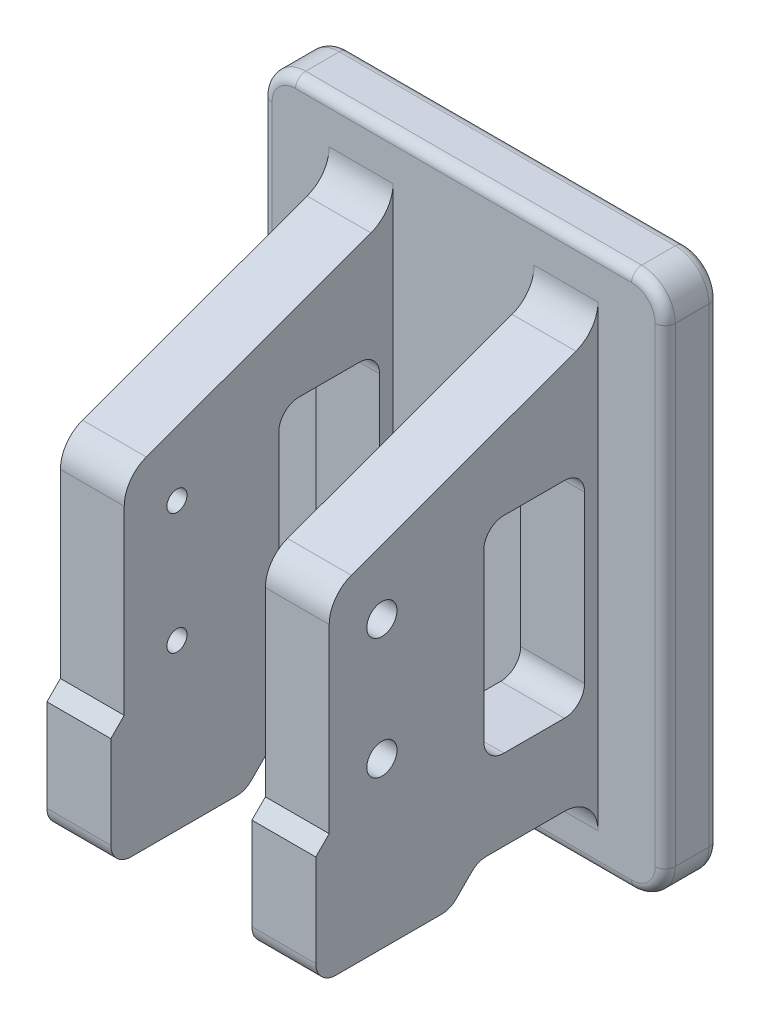
SolidWorks part; units mm, degrees
ref_plane "Front Plane" through (0, 0, 0) normal (0, 0, 1) x (1, 0, 0)
ref_plane "Top Plane" through (0, 0, 0) normal (0, 1, 0) x (1, 0, 0)
ref_plane "Right Plane" through (0, 0, 0) normal (1, 0, 0) x (0, 0, -1)
sketch "Sketch3" plane through (0, 0, 30) normal (0, 0, -1) x (-1, 0, 0)
  line L0 (95, 33.2573) -> (65, 33.2573) construction
  line L15 (80, 53.2573) -> (80, 33.2573) construction
  line L20 (55, 53.2573) -> (105, 53.2573)
  line L29 (55, -26.7427) -> (105, -26.7427)
  line L31 (110, -21.7427) -> (110, 48.2573)
  line L33 (50, -21.7427) -> (50, 48.2573)
  arc A17 (50, 48.2573) -> (55, 53.2573) centre (55, 48.2573) cw
  arc A18 (110, 48.2573) -> (105, 53.2573) centre (105, 48.2573) ccw
  arc A21 (50, -21.7427) -> (55, -26.7427) centre (55, -21.7427) ccw
  arc A22 (110, -21.7427) -> (105, -26.7427) centre (105, -21.7427) cw
  dimension "D1" = 5
extrude "Boss-Extrude1" add sketch "Sketch3" along normal blind 8
sketch "Sketch8" plane through (0, 0, 22) normal (0, 0, -1) x (-1, 0, 0)
  line L0 (50, 13.2573) -> (110, 13.2573) construction
  line L1 (50, 48.2573) -> (50, -21.7427) construction
  line L2 (110, -21.7427) -> (110, 48.2573) construction
  line L3 (80, 13.2573) -> (80, -26.7427) construction
  line L4 (55, -26.7427) -> (105, -26.7427) construction
  line L5 (78.25, 15.3786) -> (78.25, 11.136)
  line L6 (81.75, 15.3786) -> (81.75, 11.136)
  arc A0 (78.25, 11.136) -> (81.75, 11.136) centre (80, 13.2573) ccw
  arc A1 (81.75, 15.3786) -> (78.25, 15.3786) centre (80, 13.2573) ccw
extrude "Cut-Extrude3" cut sketch "Sketch8" against normal blind 3
sketch "Sketch10" plane through (0, 0, 22) normal (0, 0, -1) x (-1, 0, 0)
  line L0 (50, 13.2573) -> (110, 13.2573) construction
  line L1 (50, 48.2573) -> (50, -21.7427) construction
  line L2 (110, -21.7427) -> (110, 48.2573) construction
  line L3 (80, 13.2573) -> (80, -26.7427) construction
  line L4 (55, -26.7427) -> (105, -26.7427) construction
  line L7 (81.75, 11.136) -> (81.75, 15.3786)
  line L8 (78.25, 15.3786) -> (78.25, 11.136)
  line L9 (81.75, 11.136) -> (81.75, 15.3786)
  line L10 (78.25, 15.3786) -> (78.25, 11.136)
  circle A3 centre (80, 13.2573) radius 9.75
  arc A5 (78.25, 11.136) -> (81.75, 11.136) centre (80, 13.2573) ccw
  arc A6 (81.75, 15.3786) -> (78.25, 15.3786) centre (80, 13.2573) ccw
  arc A7 (78.25, 11.136) -> (81.75, 11.136) centre (80, 13.2573) ccw
  arc A8 (81.75, 15.3786) -> (78.25, 15.3786) centre (80, 13.2573) ccw
  dimension "D1" = 0
extrude "Boss-Extrude4" add sketch "Sketch10" along normal blind 9
fillet "Fillet2" radius 1.5 16 edges at (-80, -26.7427, 30) (-80, 53.2573, 30) (-50, 13.2573, 30) (-51.4645, 51.7928, 30) (-108.5355, 51.7928, 30) (-110, 13.2573, 30) (-80, -26.7427, 22) (-50, 13.2573, 22) (-51.4645, 51.7928, 22) (-80, 53.2573, 22) (-108.5355, 51.7928, 22) (-110, 13.2573, 22) (-108.5355, -25.2783, 22) (-51.4645, -25.2783, 22) (-108.5355, -25.2783, 30) (-51.4645, -25.2783, 30)
sketch "Sketch11" plane through (0, 0, 22) normal (0, 0, -1) x (-1, 0, 0)
  line L0 (50, 13.2573) -> (110, 13.2573) construction
  line L1 (50, -21.7427) -> (50, 48.2573) construction
  line L2 (110, 48.2573) -> (110, -21.7427) construction
  line L3 (80, 13.2573) -> (80, -26.7427) construction
  line L4 (105, -26.7427) -> (55, -26.7427) construction
  circle A0 centre (80, 13.2573) radius 11.75
extrude "Boss-Extrude5" add sketch "Sketch11" along normal blind 1
sketch "Sketch14" plane through (-70, 0, 0) normal (1, 0, 0) x (0, 0, -1)
  line L0 (-22, 1.5073) -> (-22, 25.0073) construction
  line L1 (-30, 48.2573) -> (-30, -21.7427) construction
  line L2 (-70, -1.7605) -> (-70, 28.6985)
  line L3 (-70, 28.6985) -> (-30, 43.2573)
  line L4 (-30, -16.3789) -> (-47.8764, -16.3789)
  line L6 (-30, -16.3789) -> (-30, 43.2573)
  line L7 (-47.8764, -16.3789) -> (-52, -20.5025)
  line L8 (-52, -20.5025) -> (-72, -20.5025)
  line L9 (-72, -20.5025) -> (-72, -3.7605)
  line L11 (-72, -3.7605) -> (-70, -1.7605)
  circle A6 centre (-62.1572, 3.9815) radius 1.5 construction
  circle A7 centre (-62.1572, 21.9815) radius 1.5 construction
  circle A8 centre (-62.1572, 3.9815) radius 1.5
  circle A9 centre (-62.1572, 21.9815) radius 1.5
extrude "Boss-Extrude7" add sketch "Sketch14" along normal blind 10
sketch "Sketch15" plane through (-90, 0, 0) normal (-1, 0, 0) x (0, 0, 1)
  line L4 (47.8764, -16.3789) -> (52, -20.5025)
  line L5 (70, -1.7605) -> (70, 28.6985)
  line L6 (70, 28.6985) -> (30, 43.2573)
  line L7 (30, 43.2573) -> (30, -16.3789)
  line L9 (70, -1.7605) -> (70, 28.6985)
  line L10 (70, 28.6985) -> (30, 43.2573)
  line L15 (30, 43.2573) -> (30, -16.3789)
  line L20 (47.8764, -16.3789) -> (52, -20.5025)
  line L21 (52, -20.5025) -> (72, -20.5025)
  line L22 (52, -20.5025) -> (72, -20.5025)
  line L23 (72, -20.5025) -> (72, -3.7605)
  line L24 (72, -20.5025) -> (72, -3.7605)
  line L25 (72, -3.7605) -> (70, -1.7605)
  line L26 (72, -3.7605) -> (70, -1.7605)
  line L27 (30, -16.3789) -> (47.8764, -16.3789)
  line L28 (30, -16.3789) -> (47.8764, -16.3789)
  circle A2 centre (62.1572, 3.9815) radius 1.5 construction
  circle A3 centre (62.1572, 21.9815) radius 1.5 construction
  circle A4 centre (62.1572, 3.9815) radius 1.5
  circle A5 centre (62.1572, 21.9815) radius 1.5
  dimension "D1" = 0
extrude "Boss-Extrude8" add sketch "Sketch15" along normal blind 10
fillet "Fillet3" radius 5 6 edges at (-65, 43.2573, 30) (-95, 43.2573, 30) (-95, 28.6985, 70) (-65, 28.6985, 70) (-95, -16.3789, 30) (-65, -16.3789, 30)
fillet "Fillet4" radius 3 6 edges at (-95, -20.5025, 72) (-65, -20.5025, 72) (-65, -20.5025, 52) (-95, -20.5025, 52) (-95, -16.3789, 47.8764) (-65, -16.3789, 47.8764)
sketch "Sketch16" plane through (-90, 0, 0) normal (1, 0, 0) x (0, 0, -1)
  line L8 (-72, -3.7605) -> (-72, -17.5025)
  line L9 (-69, -20.5025) -> (-53.2426, -20.5025)
  line L10 (-51.1213, -19.6238) -> (-48.7551, -17.2576)
  line L11 (-46.6337, -16.3789) -> (-35, -16.3789)
  line L12 (-30, -21.3789) -> (-30, 46.7583)
  line L13 (-33.2899, 42.0599) -> (-66.7101, 29.8959)
  line L14 (-70, 25.1974) -> (-70, -1.7605)
  line L15 (-70, -1.7605) -> (-72, -3.7605)
  line L16 (-72, -3.7605) -> (-72, -17.5025)
  line L17 (-69, -20.5025) -> (-53.2426, -20.5025)
  line L18 (-51.1213, -19.6238) -> (-48.7551, -17.2576)
  line L19 (-46.6337, -16.3789) -> (-35, -16.3789)
  line L20 (-30, -21.3789) -> (-30, 46.7583)
  line L21 (-33.2899, 42.0599) -> (-66.7101, 29.8959)
  line L22 (-70, 25.1974) -> (-70, -1.7605)
  line L23 (-70, -1.7605) -> (-72, -3.7605)
  arc A6 (-72, -17.5025) -> (-69, -20.5025) centre (-69, -17.5025) ccw
  arc A7 (-53.2426, -20.5025) -> (-51.1213, -19.6238) centre (-53.2426, -17.5025) ccw
  arc A8 (-46.6337, -16.3789) -> (-48.7551, -17.2576) centre (-46.6337, -19.3789) ccw
  arc A9 (-30, -21.3789) -> (-35, -16.3789) centre (-35, -21.3789) ccw
  arc A10 (-33.2899, 42.0599) -> (-30, 46.7583) centre (-35, 46.7583) ccw
  arc A11 (-66.7101, 29.8959) -> (-70, 25.1974) centre (-65, 25.1974) ccw
  arc A12 (-72, -17.5025) -> (-69, -20.5025) centre (-69, -17.5025) ccw
  arc A13 (-53.2426, -20.5025) -> (-51.1213, -19.6238) centre (-53.2426, -17.5025) ccw
  arc A14 (-46.6337, -16.3789) -> (-48.7551, -17.2576) centre (-46.6337, -19.3789) ccw
  arc A15 (-30, -21.3789) -> (-35, -16.3789) centre (-35, -21.3789) ccw
  arc A16 (-33.2899, 42.0599) -> (-30, 46.7583) centre (-35, 46.7583) ccw
  arc A17 (-66.7101, 29.8959) -> (-70, 25.1974) centre (-65, 25.1974) ccw
  dimension "D1" = 0
extrude "Cut-Extrude4" cut sketch "Sketch16" against normal blind 0.25
sketch "Sketch17" plane through (-70, 0, 0) normal (-1, 0, 0) x (0, 0, 1)
  line L8 (53.2426, -20.5025) -> (69, -20.5025)
  line L9 (72, -17.5025) -> (72, -3.7605)
  line L10 (72, -3.7605) -> (70, -1.7605)
  line L11 (70, -1.7605) -> (70, 25.1974)
  line L12 (66.7101, 29.8959) -> (33.2899, 42.0599)
  line L13 (30, 46.7583) -> (30, -21.3789)
  line L14 (35, -16.3789) -> (46.6337, -16.3789)
  line L15 (48.7551, -17.2576) -> (51.1213, -19.6238)
  line L16 (53.2426, -20.5025) -> (69, -20.5025)
  line L17 (72, -17.5025) -> (72, -3.7605)
  line L18 (72, -3.7605) -> (70, -1.7605)
  line L19 (70, -1.7605) -> (70, 25.1974)
  line L20 (66.7101, 29.8959) -> (33.2899, 42.0599)
  line L21 (30, 46.7583) -> (30, -21.3789)
  line L22 (35, -16.3789) -> (46.6337, -16.3789)
  line L23 (48.7551, -17.2576) -> (51.1213, -19.6238)
  arc A6 (69, -20.5025) -> (72, -17.5025) centre (69, -17.5025) ccw
  arc A7 (70, 25.1974) -> (66.7101, 29.8959) centre (65, 25.1974) ccw
  arc A8 (30, 46.7583) -> (33.2899, 42.0599) centre (35, 46.7583) ccw
  arc A9 (35, -16.3789) -> (30, -21.3789) centre (35, -21.3789) ccw
  arc A10 (48.7551, -17.2576) -> (46.6337, -16.3789) centre (46.6337, -19.3789) ccw
  arc A11 (51.1213, -19.6238) -> (53.2426, -20.5025) centre (53.2426, -17.5025) ccw
  arc A12 (69, -20.5025) -> (72, -17.5025) centre (69, -17.5025) ccw
  arc A13 (70, 25.1974) -> (66.7101, 29.8959) centre (65, 25.1974) ccw
  arc A14 (30, 46.7583) -> (33.2899, 42.0599) centre (35, 46.7583) ccw
  arc A15 (35, -16.3789) -> (30, -21.3789) centre (35, -21.3789) ccw
  arc A16 (48.7551, -17.2576) -> (46.6337, -16.3789) centre (46.6337, -19.3789) ccw
  arc A17 (51.1213, -19.6238) -> (53.2426, -20.5025) centre (53.2426, -17.5025) ccw
  dimension "D1" = 0
extrude "Cut-Extrude5" cut sketch "Sketch17" against normal blind 0.25
sketch "Sketch18" plane through (-100, 0, 0) normal (-1, 0, 0) x (0, 0, 1)
  line L0 (23.5, 53.2573) -> (28.5, 53.2573) construction
  line L1 (35, 26.2573) -> (44, 26.2573)
  line L2 (32, 23.2573) -> (32, -1.3789)
  line L3 (35, -4.3789) -> (44, -4.3789)
  line L4 (47, 23.2573) -> (47, -1.3789)
  line L5 (35, -16.3789) -> (46.6337, -16.3789) construction
  line L6 (30, 48.2573) -> (30, -21.7427) construction
  arc A0 (44, -4.3789) -> (47, -1.3789) centre (44, -1.3789) ccw
  arc A1 (32, -1.3789) -> (35, -4.3789) centre (35, -1.3789) ccw
  arc A2 (35, 26.2573) -> (32, 23.2573) centre (35, 23.2573) ccw
  arc A3 (44, 26.2573) -> (47, 23.2573) centre (44, 23.2573) cw
  point P16 (32, 26.2573)
  point P19 (47, 26.2573)
  dimension "D5" = 3
  dimension "D1" = 27
  dimension "D2" = 12
  dimension "D3" = 15
  dimension "D4" = 2
extrude "Cut-Extrude6" cut sketch "Sketch18" against normal up to surface (40 mm away) up to face at (-60, -0.7658, 53.3813)
sketch "Sketch19" plane through (-60, 0, 0) normal (1, 0, 0) x (0, 0, -1)
  circle A0 centre (-62.1572, 21.9815) radius 2.25
  circle A1 centre (-62.1572, 3.9815) radius 2.25
extrude "Cut-Extrude7" cut sketch "Sketch19" against normal blind 4
chamfer "Chamfer1" distance 1.5 angle 45 2 edges at (-100, 2.4815, 62.1572) (-100, 20.4815, 62.1572)
sketch "Sketch20" plane through (0, 0, 72) normal (0, 0, 1) x (1, 0, 0)
  line L0 (-105, 53.2573) -> (-55, 53.2573) construction
  line L1 (-90.5, 53.2573) -> (-69.5, 53.2573)
  line L2 (-90.5, 53.2573) -> (-90.5, -26.7427)
  line L3 (-90.5, -26.7427) -> (-69.5, -26.7427)
  line L4 (-69.5, 53.2573) -> (-69.5, -26.7427)
  line L5 (-55, -26.7427) -> (-105, -26.7427) construction
  line L6 (-69.75, 46.7583) -> (-69.75, 42.0599) construction
  line L7 (-90.25, 42.0599) -> (-90.25, 29.8959) construction
  dimension "D1" = 0.25
  dimension "D2" = 0.25
extrude "Cut-Extrude8" cut sketch "Sketch20" against normal up to surface (42 mm away) up to face at (-95.125, 12.6897, 30)
